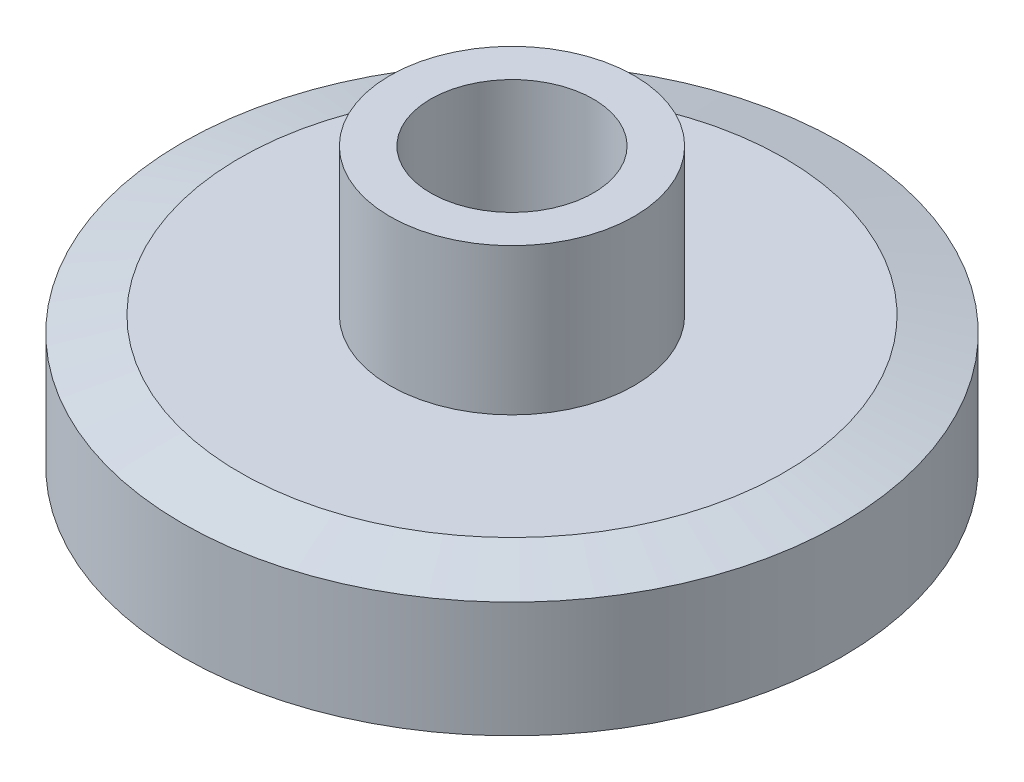
SolidWorks part; units mm, degrees
material "Сталь ШХ15 ГОСТ 801-78"
ref_plane "Plane1" through (0, 0, 0) normal (0, 0, 1) x (1, 0, 0)
ref_plane "Plane2" through (0, 0, 0) normal (0, 1, 0) x (1, 0, 0)
ref_plane "Plane3" through (0, 0, 0) normal (1, 0, 0) x (0, 0, -1)
sketch "Эскиз2" plane through (0, 0, 0) normal (0, 0, 1) x (1, 0, 0)
  line L0 (0, 0) -> (8.1, 0)
  line L1 (8.1, 0) -> (8.1, 3.6)
  line L2 (8.1, 3.6) -> (3, 3.6)
  line L3 (3, 3.6) -> (3, 7.2)
  line L4 (3, 7.2) -> (0, 7.2)
  line L5 (0, 7.2) -> (0, 0)
  dimension "D1" = 8.1
  dimension "D2" = 3.6
  dimension "3.6" = 3.6
  dimension "D4" = 3
ref_axis "Ось1" through (0, 7.2, 0) along (0, -1, 0)
revolve "Повернуть2" add sketch "Эскиз2" angle 360 about axis through (0, 7.2, 0) along (0, -1, 0) other way angle 360
chamfer "Фаска2" distance 1.41 angle 15 1 edges at (0, 3.6, 8.1) first distance on face at (0, 3.6, 3)
chamfer "Фаска3" distance 1.41 angle 15 1 edges at (0, 0, 8.1) first distance on face at (0, 0, 8.1)
sketch "Эскиз4" plane through (0, 7.2, 0) normal (0, 1, 0) x (1, 0, 0)
  circle A0 centre (0, 0) radius 2
  dimension "D1" = 4
extrude "Вырез-Вытянуть2" cut sketch "Эскиз4" against normal through all both contours A0
